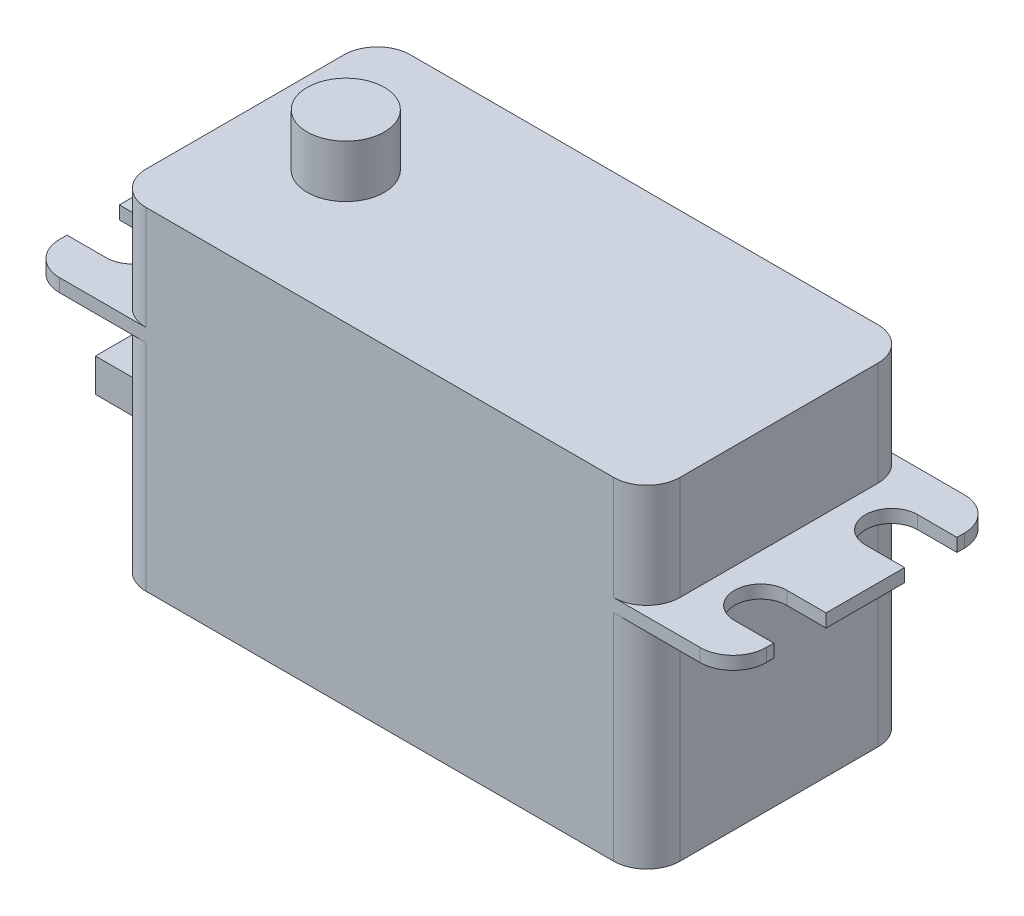
SolidWorks part; units mm, degrees
ref_plane "Front Plane" through (0, 0, 0) normal (0, 0, 1) x (1, 0, 0)
ref_plane "Top Plane" through (0, 0, 0) normal (0, 1, 0) x (1, 0, 0)
ref_plane "Right Plane" through (0, 0, 0) normal (1, 0, 0) x (0, 0, -1)
sketch "Sketch1" plane through (0, 0, 0) normal (0, 1, 0) x (1, 0, 0)
  line L0 (-16.17, 0) -> (16.17, 0) construction
  line L1 (-24.46, -10.1) -> (24.46, -10.1)
  line L2 (-27, -7.56) -> (-27, 7.56)
  line L3 (-24.46, 10.1) -> (24.46, 10.1)
  line L4 (27, -7.56) -> (27, 7.56)
  line L5 (-27, -10.1) -> (27, 10.1) construction
  line L6 (-27, 10.1) -> (27, -10.1) construction
  line L7 (0, -11.11) -> (0, 11.11) construction
  line L8 (24, 3) -> (27, 3)
  line L9 (24, 7) -> (27, 7)
  line L10 (27, 7) -> (27, 3)
  line L11 (24, -3) -> (27, -3)
  line L12 (24, -7) -> (27, -7)
  line L13 (27, -7) -> (27, -3)
  line L14 (-24, 7) -> (-27, 7)
  line L15 (-24, 3) -> (-27, 3)
  line L16 (-27, 3) -> (-27, 7)
  line L17 (-24, -7) -> (-27, -7)
  line L18 (-24, -3) -> (-27, -3)
  line L19 (-27, -3) -> (-27, -7)
  arc A0 (24, 7) -> (24, 3) centre (24, 5) ccw
  arc A1 (24, -7) -> (24, -3) centre (24, -5) cw
  arc A2 (-24, -7) -> (-24, -3) centre (-24, -5) ccw
  arc A3 (-24, 7) -> (-24, 3) centre (-24, 5) cw
  arc A4 (-24.46, -10.1) -> (-27, -7.56) centre (-24.46, -7.56) cw
  arc A5 (24.46, -10.1) -> (27, -7.56) centre (24.46, -7.56) ccw
  arc A6 (24.46, 10.1) -> (27, 7.56) centre (24.46, 7.56) cw
  arc A7 (-27, 7.56) -> (-24.46, 10.1) centre (-24.46, 7.56) cw
  point P0 (0, 0)
  dimension "D3" = 4
  dimension "D6" = 2.54
  dimension "D1" = 54
  dimension "D2" = 20.2
  dimension "D4" = 48
  dimension "D5" = 10
extrude "Boss-Extrude1" add sketch "Sketch1" along normal blind 1 contours A7 L2 L14 A3 L15 L18 A2 L17 A4 L1 A5 L4 L12 A1 L11 L8 A0 L9 A6 L3 region at (0, 0, 0)
sketch "Sketch3" plane through (0, 1, 0) normal (0, 1, 0) x (1, 0, 0)
  line L1 (-17.86, -10.1) -> (17.86, -10.1)
  line L2 (-20.4, -7.56) -> (-20.4, 7.56)
  line L3 (-17.86, 10.1) -> (17.86, 10.1)
  line L4 (20.4, -7.56) -> (20.4, 7.56)
  line L5 (-20.4, -10.1) -> (20.4, 10.1) construction
  line L6 (-20.4, 10.1) -> (20.4, -10.1) construction
  arc A0 (-17.86, -10.1) -> (-20.4, -7.56) centre (-17.86, -7.56) cw
  arc A1 (17.86, -10.1) -> (20.4, -7.56) centre (17.86, -7.56) ccw
  arc A2 (17.86, 10.1) -> (20.4, 7.56) centre (17.86, 7.56) cw
  arc A3 (-20.4, 7.56) -> (-17.86, 10.1) centre (-17.86, 7.56) cw
  point P0 (0, 0)
  dimension "D3" = 2.54
  dimension "D1" = 40.8
  dimension "D2" = 20.2
extrude "Boss-Extrude2" add sketch "Sketch3" along normal blind 7.95
sketch "Sketch4" plane through (0, 0, 0) normal (0, -1, 0) x (1, 0, 0)
  line L1 (-17.86, -10.1) -> (17.86, -10.1)
  line L2 (-20.4, -7.56) -> (-20.4, 7.56)
  line L3 (-17.86, 10.1) -> (17.86, 10.1)
  line L4 (20.4, -7.56) -> (20.4, 7.56)
  line L5 (-20.4, -10.1) -> (20.4, 10.1) construction
  line L6 (-20.4, 10.1) -> (20.4, -10.1) construction
  arc A0 (-17.86, -10.1) -> (-20.4, -7.56) centre (-17.86, -7.56) cw
  arc A1 (17.86, -10.1) -> (20.4, -7.56) centre (17.86, -7.56) ccw
  arc A2 (17.86, 10.1) -> (20.4, 7.56) centre (17.86, 7.56) cw
  arc A3 (-20.4, 7.56) -> (-17.86, 10.1) centre (-17.86, 7.56) cw
  point P0 (0, 0)
  dimension "D3" = 2.54
  dimension "D1" = 20.2
  dimension "D2" = 40.8
extrude "Boss-Extrude3" add sketch "Sketch4" along normal blind 16.45
sketch "Sketch5" plane through (-20.4, 0, 0) normal (-1, 0, 0) x (0, 0, 1)
  line L0 (-0.8843, -9.5287) -> (-0.8843, -11.2259)
  line L1 (-3.81, -11.6473) -> (3.81, -11.6473)
  line L2 (-3.81, -11.6473) -> (-3.81, -9.1073)
  line L3 (-3.81, -9.1073) -> (3.81, -9.1073)
  line L4 (3.81, -11.6473) -> (3.81, -9.1073)
  line L5 (-3.4243, -9.5287) -> (-1.6557, -9.5287)
  line L6 (-3.4243, -9.5287) -> (-3.4243, -11.2259)
  line L7 (-3.4243, -11.2259) -> (-1.6557, -11.2259)
  line L8 (-1.6557, -9.5287) -> (-1.6557, -11.2259)
  line L9 (-0.8843, -9.5287) -> (0.8843, -9.5287)
  line L10 (0.8843, -9.5287) -> (0.8843, -11.2259)
  line L11 (-0.8843, -11.2259) -> (0.8843, -11.2259)
  line L12 (1.6557, -9.5287) -> (1.6557, -11.2259)
  line L13 (1.6557, -9.5287) -> (3.4243, -9.5287)
  line L14 (3.4243, -9.5287) -> (3.4243, -11.2259)
  line L15 (1.6557, -11.2259) -> (3.4243, -11.2259)
  point P8 (0, -11.6473)
  point P18 (-3.4243, -10.3773)
  point P19 (-3.81, -10.3773)
  point P20 (0, -11.2259)
  dimension "D2" = 2.54
  dimension "D3" = 2.54
  dimension "D4" = 7.62
  dimension "D1" = 3
extrude "Boss-Extrude4" add sketch "Sketch5" along normal blind 7.62
sketch "Sketch6" plane through (0, 8.95, 0) normal (0, 1, 0) x (1, 0, 0)
  circle A0 centre (-12.7, 0) radius 2.95
  dimension "D1" = 5.9
  dimension "D2" = 12.7
extrude "Boss-Extrude5" add sketch "Sketch6" along normal blind 4
other "CPoint1" parameters "Diameter"=25.4, "StubLength"=38.1
ref_axis "Axis1" through (-38.02, -11.2259, -3.4243) along (1, 0, 0)
other "CPoint2" parameters "Diameter"=25.4, "StubLength"=38.1
ref_axis "Axis2" through (-38.02, -11.2259, -0.8843) along (1, 0, 0)
other "CPoint3" parameters "Diameter"=25.4, "StubLength"=38.1
ref_axis "Axis3" through (-38.02, -11.2259, 1.6557) along (1, 0, 0)
equation "\"Bodytube_OD\"= 6.17in"
equation "\"Bodytube_ID\"= 5.998in"
equation "\"Motor_OD\"= 4in"
equation "\"Fwd_Tube_Length\"= 40in"
equation "\"Mid_Tube_Length\"= 1in"
equation "\"Aft_Section_Length\"= 39in"
equation "\"AB_Coupler_OD_Length\"= 1in"
equation "\"AB_Coupling_Section_Length\"= 0.375in"
equation "\"AB_Coupler_Length\"= \"AB_Coupler_OD_Length\" + \"AB_Coupling_Section_Length\" * 2"
equation "\"Cutout_Angle\"= 80"
equation "\"AB_Paddle_Height\"= 0.375in"
equation "\"AB_Coupler_Num_Screws\"= 6"
equation "\"Num_Cutouts\"= 3"
equation "\"AB_Coupler_OD\"= 6.17in"
equation "\"AB_Coupler_ID\"= 5.75in"
equation "\"AB_Coupler_Surface_Diameter\"= 5.998in"
equation "\"AB_Coupling_Screw_Diameter\"= 0.1065in"
equation "\"AB_Central_Bushing_Length\"= .75in"
equation "\"Lead_Screw_Dist\"= 2.25in"
equation "\"Lead_Screw_Diam\"= 11mm"
equation "\"Paddle_Pin_Offset\"= .25in"
equation "\"Paddle_Pin_Radius\"= 2.25in"
equation "\"Paddle_Gear_OD\"= 3.2in"
equation "\"Drive_Gear_OD\"= 1.7in"
equation "\"Fwd_BKHD_From_Top\"= 18in"
equation "\"Fin_Thickness\"= .118in"
equation "\"Guiderail_Cutout_Diameter\"= 1.5in"
equation "\"DB9_Hole_Dist\"= 25mm"
equation "\"Airbrakes_Wire_Hole_Dia\"= .25in"
equation "\"Airbrakes_Wire_Hole_Dist\"= 1.1in"
equation "\"Servo_Gear_Offset\"= 0.5in"
equation "\"D2@Sketch6\"=\"Servo_Gear_Offset\""
